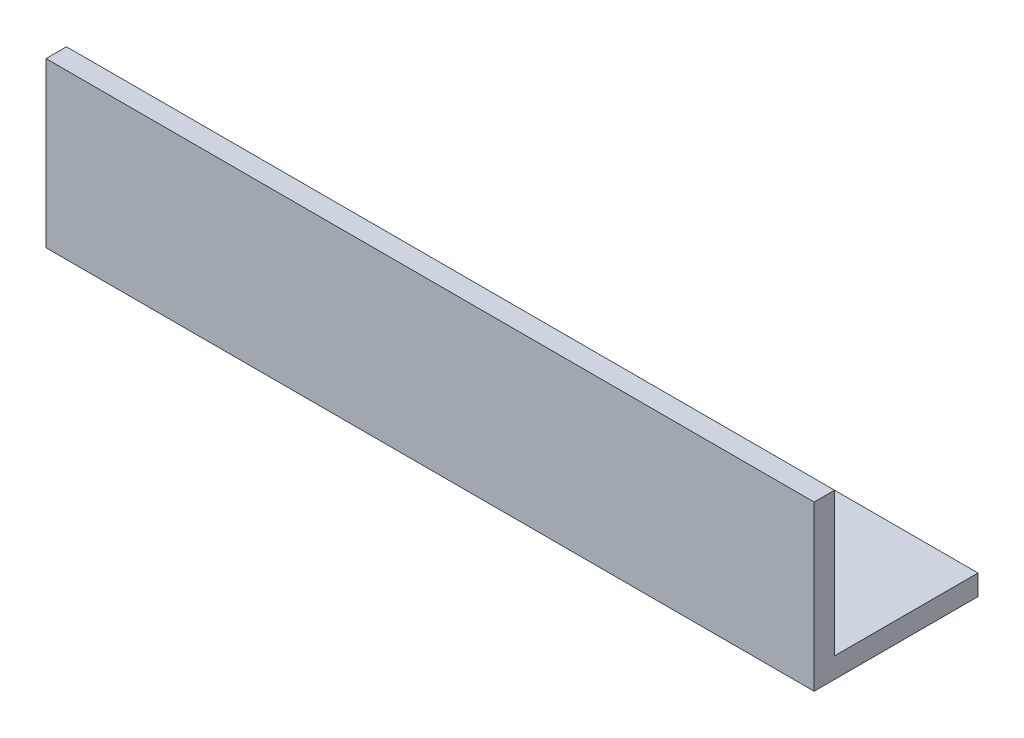
SolidWorks part; units mm, degrees
ref_plane "Спереди" through (0, 0, 0) normal (0, 0, 1) x (1, 0, 0)
ref_plane "Сверху" through (0, 0, 0) normal (0, 1, 0) x (1, 0, 0)
ref_plane "Справа" through (0, 0, 0) normal (1, 0, 0) x (0, 0, -1)
sketch "Эскиз1" plane through (0, 0, 0) normal (1, 0, 0) x (0, 0, -1)
  line L0 (0, 0) -> (0, 32)
  line L1 (0, 0) -> (32, 0)
extrude "Вытянуть-Тонкостенный1" add sketch "Эскиз1" along normal blind 150 thin thin type one direction reverse wall 4
sketch "Эскиз2" plane through (0, 0, 0) normal (0, -1, 0) x (1, 0, 0)
  line L0 (75, -34.4537) -> (75, 3.8067) construction
  circle A0 centre (130, -13) radius 5
  circle A1 centre (100, -13) radius 5
  circle A2 centre (50, -13) radius 5
  circle A3 centre (20, -13) radius 5
  dimension "D1" = 2
extrude "Вырез-Вытянуть1" cut sketch "Эскиз2" against normal through all
